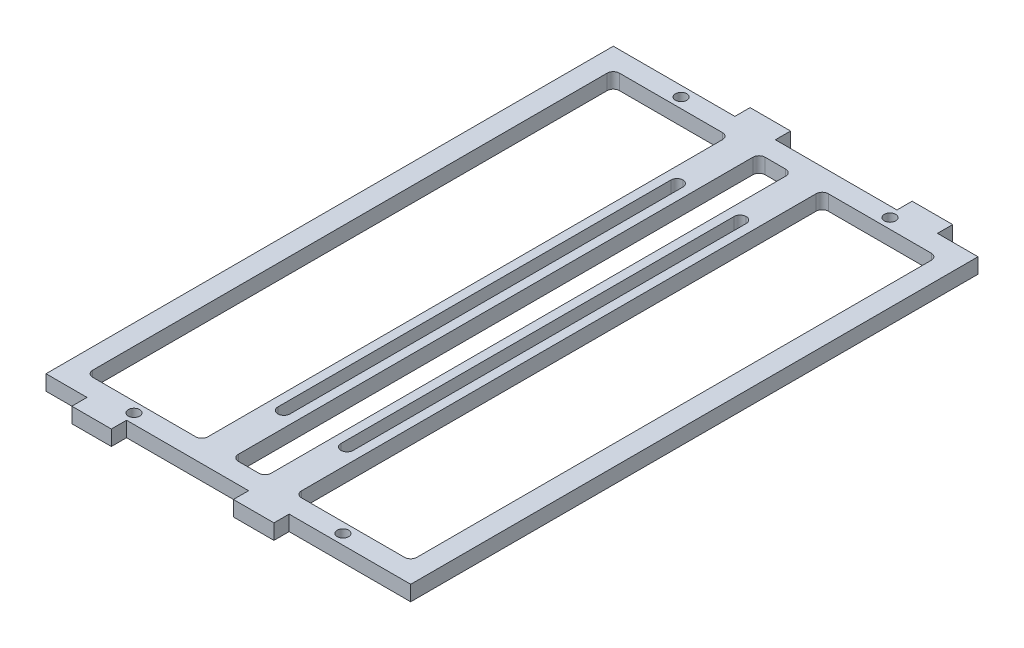
SolidWorks part; units mm, degrees
material "6061-T6 (SS)"
ref_plane "Front Plane" through (0, 0, 0) normal (0, 0, 1) x (1, 0, 0)
ref_plane "Top Plane" through (0, 0, 0) normal (0, 1, 0) x (1, 0, 0)
ref_plane "Right Plane" through (0, 0, 0) normal (1, 0, 0) x (0, 0, -1)
sketch "Sketch1" plane through (0, 0, 0) normal (0, 1, 0) x (1, 0, 0)
  line L0 (50.8, 82.55) -> (-50.8, 82.55)
  line L1 (57.15, 88.9) -> (-57.15, 88.9)
  line L2 (57.15, 88.9) -> (57.15, -88.9)
  line L3 (57.15, -88.9) -> (-57.15, -88.9)
  line L4 (-57.15, 88.9) -> (-57.15, -88.9)
  line L5 (57.15, 88.9) -> (-57.15, -88.9) construction
  line L6 (57.15, -88.9) -> (-57.15, 88.9) construction
  line L7 (-50.8, 82.55) -> (-50.8, -82.55)
  line L8 (50.8, -82.55) -> (-50.8, -82.55)
  line L9 (50.8, 82.55) -> (50.8, -82.55)
  point P0 (0, 0)
  dimension "D1" = 114.3
  dimension "D2" = 177.8
  dimension "D3" = 6.35
extrude "Boss-Extrude1" add sketch "Sketch1" along normal blind 4.7625
sketch "Sketch2" plane through (0, 0, 88.9) normal (0, 0, 1) x (1, 0, 0)
  line L0 (-57.15, 2.3813) -> (57.15, 2.3813) construction
  line L1 (-57.15, 4.7625) -> (-57.15, 0) construction
  line L2 (57.15, 4.7625) -> (57.15, 0) construction
  line L3 (-57.15, 0) -> (57.15, 0) construction
  line L4 (-31.9066, 4.7625) -> (-44.2934, 4.7625)
  line L5 (-31.9066, 4.7625) -> (-31.9066, 0)
  line L6 (-31.9066, 0) -> (-44.2934, 0)
  line L7 (-44.2934, 4.7625) -> (-44.2934, 0)
  line L8 (-31.9066, 4.7625) -> (-44.2934, 0) construction
  line L9 (-31.9066, 0) -> (-44.2934, 4.7625) construction
  line L11 (19.05, 4.7625) -> (6.35, 4.7625)
  line L12 (19.05, 4.7625) -> (19.05, 0)
  line L13 (19.05, 0) -> (6.35, 0)
  line L14 (6.35, 4.7625) -> (6.35, 0)
  line L15 (19.05, 4.7625) -> (6.35, 0) construction
  line L16 (19.05, 0) -> (6.35, 4.7625) construction
  point P6 (-38.1, 2.3813)
  point P13 (12.7, 2.3813)
  dimension "D1" = 19.05
  dimension "D2" = 50.8
  dimension "D3" = 12.7
extrude "Boss-Extrude2" add sketch "Sketch2" along normal blind 4.7625
sketch "Sketch3" plane through (0, 0, -88.9) normal (0, 0, -1) x (-1, 0, 0)
  line L0 (-57.15, 2.3813) -> (57.15, 2.3813) construction
  line L1 (-57.15, 4.7625) -> (-57.15, 0) construction
  line L2 (57.15, 4.7625) -> (57.15, 0) construction
  line L3 (-57.15, 0) -> (57.15, 0) construction
  line L4 (-31.75, 4.7625) -> (-44.45, 4.7625)
  line L5 (-31.75, 4.7625) -> (-31.75, 0)
  line L6 (-31.75, 0) -> (-44.45, 0)
  line L7 (-44.45, 4.7625) -> (-44.45, 0)
  line L8 (-31.75, 4.7625) -> (-44.45, 0) construction
  line L9 (-31.75, 0) -> (-44.45, 4.7625) construction
  line L11 (19.05, 4.7625) -> (6.35, 4.7625)
  line L12 (19.05, 4.7625) -> (19.05, 0)
  line L13 (19.05, 0) -> (6.35, 0)
  line L14 (6.35, 4.7625) -> (6.35, 0)
  line L15 (19.05, 4.7625) -> (6.35, 0) construction
  line L16 (19.05, 0) -> (6.35, 4.7625) construction
  point P6 (-38.1, 2.3812)
  point P13 (12.7, 2.3812)
  dimension "D1" = 12.7
  dimension "D2" = 12.7
  dimension "D3" = 19.05
  dimension "D4" = 50.8
extrude "Boss-Extrude3" add sketch "Sketch3" along normal blind 4.7625
sketch "Sketch4" plane through (0, 4.7625, 0) normal (0, 1, 0) x (-1, 0, 0)
  line L0 (57.15, 0) -> (-57.15, 0) construction
  line L1 (57.15, -88.9) -> (57.15, 88.9) construction
  line L2 (-57.15, 88.9) -> (-57.15, -88.9) construction
  line L3 (57.15, 88.9) -> (44.2934, 88.9) construction
  line L4 (5.1435, -88.9) -> (14.6685, -88.9)
  line L5 (5.1435, -88.9) -> (5.1435, 88.9)
  line L6 (5.1435, 88.9) -> (14.6685, 88.9)
  line L7 (14.6685, -88.9) -> (14.6685, 88.9)
  line L8 (5.1435, -88.9) -> (14.6685, 88.9) construction
  line L9 (5.1435, 88.9) -> (14.6685, -88.9) construction
  line L10 (-19.05, 88.9) -> (-57.15, 88.9) construction
  line L11 (-14.6685, -88.9) -> (-5.1435, -88.9)
  line L12 (-14.6685, -88.9) -> (-14.6685, 88.9)
  line L13 (-14.6685, 88.9) -> (-5.1435, 88.9)
  line L14 (-5.1435, -88.9) -> (-5.1435, 88.9)
  line L15 (-14.6685, -88.9) -> (-5.1435, 88.9) construction
  line L16 (-14.6685, 88.9) -> (-5.1435, -88.9) construction
  line L18 (8.001, -63.5) -> (11.811, -63.5)
  line L19 (8.001, -63.5) -> (8.001, 63.5)
  line L20 (8.001, 63.5) -> (11.811, 63.5)
  line L21 (11.811, -63.5) -> (11.811, 63.5)
  line L22 (8.001, -63.5) -> (11.811, 63.5) construction
  line L23 (8.001, 63.5) -> (11.811, -63.5) construction
  line L24 (-11.811, -63.5) -> (-8.001, -63.5)
  line L25 (-11.811, -63.5) -> (-11.811, 63.5)
  line L26 (-11.811, 63.5) -> (-8.001, 63.5)
  line L27 (-8.001, -63.5) -> (-8.001, 63.5)
  line L28 (-11.811, -63.5) -> (-8.001, 63.5) construction
  line L29 (-11.811, 63.5) -> (-8.001, -63.5) construction
  point P6 (9.906, 0)
  point P13 (-9.906, 0)
  point P20 (9.906, 0)
  point P26 (-9.906, 0)
  dimension "D1" = 9.525
  dimension "D2" = 9.525
  dimension "D3" = 9.906
  dimension "D4" = 9.906
  dimension "D5" = 127
  dimension "D6" = 3.81
  dimension "D7" = 127
  dimension "D8" = 3.81
extrude "Boss-Extrude4" add sketch "Sketch4" against normal blind 4.7625
fillet "Fillet1" radius 1.905 20 edges at (-8.001, 2.3813, -63.5) (-11.811, 2.3813, -63.5) (8.001, 2.3813, -63.5) (11.811, 2.3813, -63.5) (-8.001, 2.3813, 63.5) (-11.811, 2.3813, 63.5) (8.001, 2.3813, 63.5) (11.811, 2.3813, 63.5) (-5.1435, 2.3813, 82.55) (5.1435, 2.3813, 82.55) (-5.1435, 2.3813, -82.55) (5.1435, 2.3813, -82.55) (-14.6685, 2.3813, -82.55) (-50.8, 2.3813, -82.55) (-50.8, 2.3813, 82.55) (-14.6685, 2.3813, 82.55) (14.6685, 2.3813, 82.55) (50.8, 2.3813, 82.55) (14.6685, 2.3813, -82.55) (50.8, 2.3813, -82.55)
hole_wizard "9/64 (0.14063) Diameter Hole1" positions "Sketch7" profile "Sketch6" hole size "9/64" standard "Ansi Inch" end condition through all
sketch "Sketch7" plane through (0, 4.7625, 0) normal (0, 1, 0) x (-1, 0, 0)
  line L0 (32.7343, -88.9) -> (32.7343, -82.55) construction
  line L1 (19.05, -88.9) -> (57.15, -88.9) construction
  line L2 (16.5735, -82.55) -> (48.895, -82.55) construction
  line L4 (50.8, -85.725) -> (14.6685, -85.725) construction
  line L5 (50.8, -80.645) -> (50.8, 80.645) construction
  line L6 (14.6685, -80.645) -> (14.6685, 80.645) construction
  line L8 (-14.6685, 80.645) -> (-14.6685, -80.645) construction
  line L9 (-14.6685, -85.725) -> (-50.8, -85.725) construction
  line L10 (-50.8, 80.645) -> (-50.8, -80.645) construction
  line L12 (-32.7343, -88.9) -> (-32.7343, -82.55) construction
  line L13 (-31.75, -88.9) -> (6.35, -88.9) construction
  line L14 (-48.895, -82.55) -> (-16.5735, -82.55) construction
  line L16 (50.8, 85.725) -> (14.6685, 85.725) construction
  line L18 (-14.6685, 85.725) -> (-50.8, 85.725) construction
  line L20 (32.7343, 82.55) -> (32.7343, 88.9) construction
  line L21 (48.895, 82.55) -> (16.5735, 82.55) construction
  line L22 (31.9066, 88.9) -> (-6.35, 88.9) construction
  line L24 (-32.7343, 82.55) -> (-32.7343, 88.9) construction
  line L25 (-16.5735, 82.55) -> (-48.895, 82.55) construction
  line L26 (-19.05, 88.9) -> (-57.15, 88.9) construction
  point P0 (32.7343, -85.725)
  point P1 (-32.7343, -85.725)
  point P3 (32.7343, 85.725)
  point P5 (-32.7343, 85.725)
  point P30 (32.7343, -85.725)
  point P39 (-32.7343, -85.725)
  point P62 (32.7343, 85.725)
  point P63 (-32.7343, 85.725)
sketch "Sketch6" plane through (-32.7343, 4.7625, -85.725) normal (1, 0, 0) x (0, 0, 1)
  line L0 (0, 0) -> (0, 4.7626)
  line L1 (0, 4.7626) -> (1.786, 4.7626)
  line L2 (1.786, 4.7626) -> (1.786, 0)
  line L5 (1.786, 0) -> (0, 0)
  line L11 (0, -6.35) -> (0, 107.95) construction
  dimension "Thru Hole Dia." = 3.572
  dimension "Thru Hole Depth" = 4.7626
